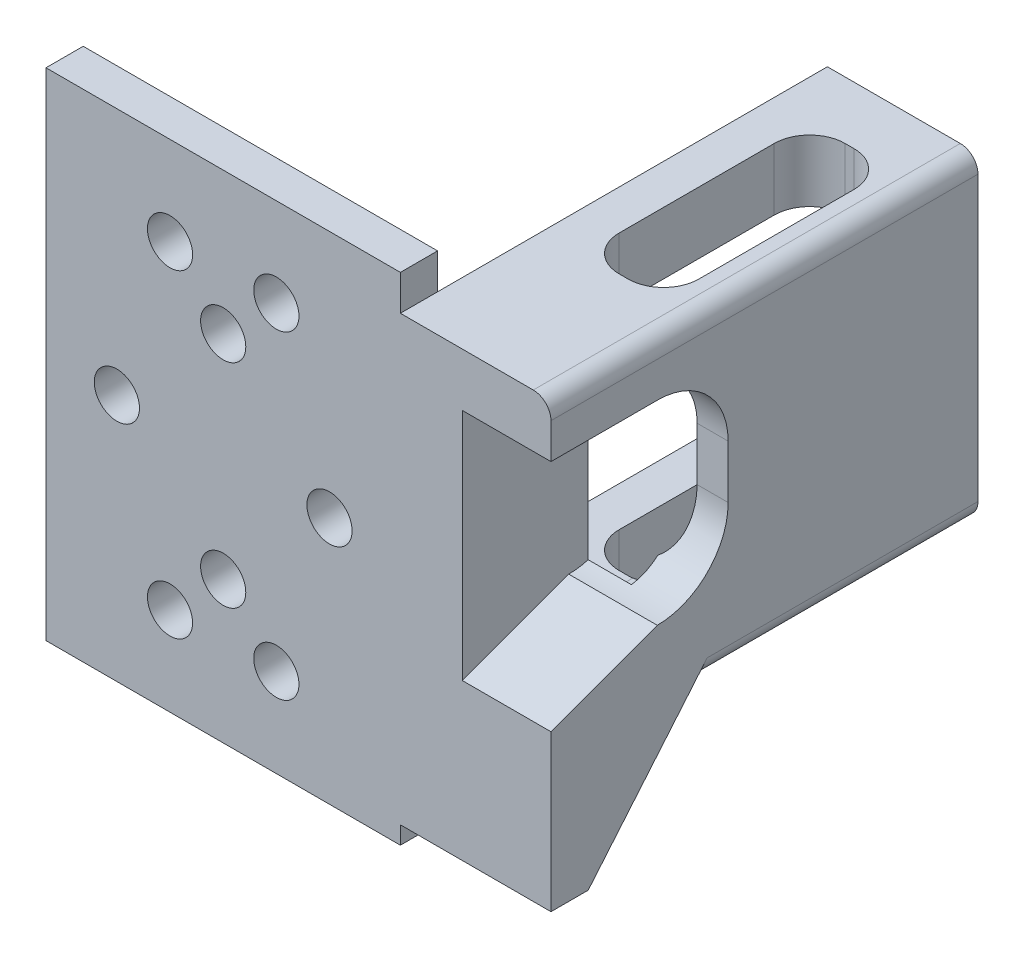
SolidWorks part; units mm, degrees
ref_plane "Front Plane" through (0, 0, 0) normal (0, 0, 1) x (1, 0, 0)
ref_plane "Top Plane" through (0, 0, 0) normal (0, 1, 0) x (1, 0, 0)
ref_plane "Right Plane" through (0, 0, 0) normal (1, 0, 0) x (0, 0, -1)
sketch "Sketch1" plane through (0, 0, 0) normal (0, 0, 1) x (1, 0, 0)
  line L0 (0, 14) -> (20, 14) construction
  line L1 (0, 0) -> (20, 0)
  line L2 (0, 0) -> (0, 28)
  line L3 (0, 28) -> (20, 28)
  line L4 (20, 0) -> (20, 28)
  line L5 (10, 28) -> (10, 0) construction
  line L7 (20, 1) -> (28.5, 1)
  line L8 (20, 1) -> (20, 26)
  line L9 (20, 26) -> (28.5, 26)
  line L10 (28.5, 1) -> (28.5, 26)
  circle A0 centre (10, 20) radius 1.275
  circle A1 centre (7, 23) radius 1.275
  circle A2 centre (4, 14) radius 1.275
  circle A3 centre (16, 14) radius 1.275
  circle A4 centre (13, 23) radius 1.275
  circle A5 centre (13, 5) radius 1.275
  circle A6 centre (10, 8) radius 1.275
  circle A7 centre (7, 5) radius 1.275
  dimension "D8" = 2.55
  dimension "D1" = 20
  dimension "D2" = 28
  dimension "D3" = 2
  dimension "D4" = 1
  dimension "D5" = 8.5
  dimension "D6" = 8
  dimension "D7" = 4
  dimension "D9" = 7
  dimension "D10" = 5
extrude "Boss-Extrude1" add sketch "Sketch1" against normal blind 2.1 contours L1 L4 L3 L2 A6 A5 A3 A2 A1 A0 A4 A7 region at (10, 14, 0)
extrude "Boss-Extrude2" add sketch "Sketch1<3>" against normal blind 24.1 contours L7 L10 L9 L4 region at (24.25, 13.5, 0)
sketch "Sketch1<3>" plane through (0, 0, 0) normal (0, 0, 1) x (1, 0, 0) same geometry as "Sketch1"
sketch "Sketch2" plane through (28.5, 0, 0) normal (1, 0, 0) x (0, 0, -1)
  line L0 (0, 23) -> (6, 23)
  line L1 (0, 1) -> (0, 26) construction
  line L2 (10, 19) -> (10, 16)
  line L3 (6, 12) -> (0, 9.797)
  line L4 (0, 9.797) -> (0, 23)
  line L5 (24.1, 1) -> (0, 1) construction
  arc A0 (10, 16) -> (6, 12) centre (6, 16) cw
  arc A1 (6, 23) -> (10, 19) centre (6, 19) cw
  dimension "D1" = 4
  dimension "D2" = 6
  dimension "D3" = 3
  dimension "D4" = 13.203
  dimension "D5" = 8.797
extrude "Cut-Extrude1" cut sketch "Sketch2" against normal blind 5
sketch "Sketch3" plane through (0, 26, 0) normal (0, 1, 0) x (1, 0, 0)
  line L0 (20, 24.1) -> (20, 2.1) construction
  line L1 (24.75, 20.85) -> (24.25, 20.85)
  line L2 (26.75, 18.85) -> (26.75, 10.1)
  line L3 (24.75, 8.1) -> (24.25, 8.1)
  line L4 (22.25, 18.85) -> (22.25, 10.1)
  line L5 (20, 24.1) -> (28.5, 24.1) construction
  arc A0 (24.75, 20.85) -> (26.75, 18.85) centre (24.75, 18.85) cw
  arc A1 (24.25, 8.1) -> (22.25, 10.1) centre (24.25, 10.1) cw
  arc A2 (26.75, 10.1) -> (24.75, 8.1) centre (24.75, 10.1) cw
  arc A3 (24.25, 20.85) -> (22.25, 18.85) centre (24.25, 18.85) ccw
  point P11 (26.75, 20.85)
  point P14 (22.25, 8.1)
  point P17 (26.75, 8.1)
  dimension "D5" = 2
  dimension "D1" = 12.75
  dimension "D2" = 4.5
  dimension "D3" = 2.25
  dimension "D4" = 3.25
extrude "Cut-Extrude2" cut sketch "Sketch3" against normal through all and the other way through all
sketch "Sketch4" plane through (0, 0, -24.1) normal (0, 0, -1) x (-1, 0, 0)
  line L0 (-20, 1) -> (-20, 26) construction
  line L1 (-20, 11.5) -> (-25, 11.5)
  line L2 (-20, 11.5) -> (-20, 22.5)
  line L3 (-20, 22.5) -> (-25, 22.5)
  line L4 (-26, 12.5) -> (-26, 21.5)
  line L6 (-20, 26) -> (-28.5, 26) construction
  arc A0 (-25, 11.5) -> (-26, 12.5) centre (-25, 12.5) cw
  arc A1 (-25, 22.5) -> (-26, 21.5) centre (-25, 21.5) ccw
  point P11 (-26, 11.5)
  point P14 (-26, 22.5)
  dimension "D4" = 1
  dimension "D1" = 6
  dimension "D2" = 11
  dimension "D3" = 3.5
extrude "Cut-Extrude3" cut sketch "Sketch4" against normal blind 17
sketch "Sketch6" plane through (28.5, 0, 0) normal (1, 0, 0) x (0, 0, -1)
  line L0 (2.1, 1) -> (24.1, 1)
  line L1 (24.1, 1) -> (0, 1) construction
  line L2 (24.1, 1) -> (24.1, 8)
  line L3 (24.1, 1) -> (24.1, 26) construction
  line L4 (24.1, 8) -> (7.9737, 8)
  line L5 (7.9737, 8) -> (2.1, 1)
  line L6 (0, 1) -> (0, 9.797) construction
  dimension "D1" = 2.1
  dimension "D2" = 7
  dimension "D3" = 50
extrude "Cut-Extrude4" cut sketch "Sketch6" against normal up to next
fillet "Fillet1" radius 1 2 edges at (28.5, 8, -16.0368) (28.5, 26, -12.05)
